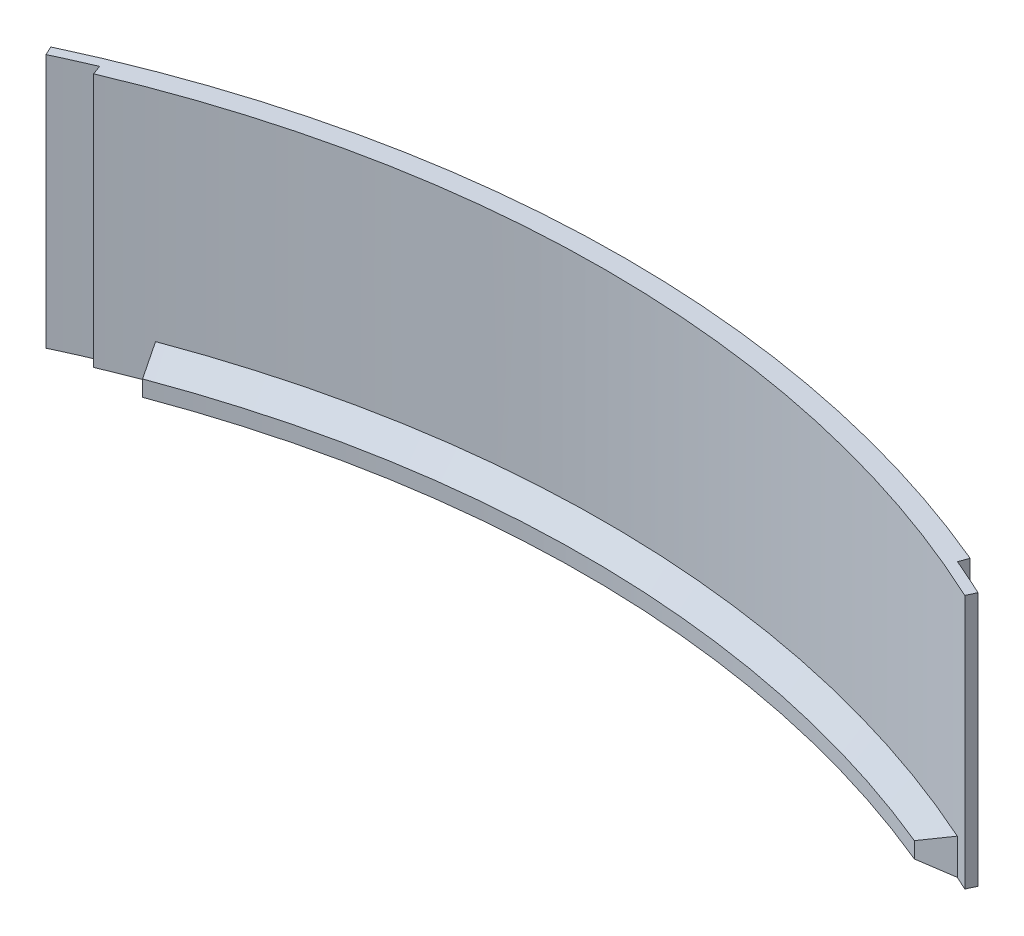
SolidWorks part; units mm, degrees
ref_plane "Front Plane" through (0, 0, 0) normal (0, 0, 1) x (1, 0, 0)
ref_plane "Top Plane" through (0, 0, 0) normal (0, 1, 0) x (1, 0, 0)
ref_plane "Right Plane" through (0, 0, 0) normal (1, 0, 0) x (0, 0, -1)
sketch "Sketch2" plane through (0, 0, 0) normal (0, 1, 0) x (1, 0, 0)
  line L0 (0, 0) -> (0, 184.9275) construction
  line L1 (-58.6379, 125.7494) -> (-59.1666, 126.8831)
  line L2 (58.11, 124.6173) -> (58.6379, 125.7494)
  line L3 (0, 0) -> (-58.11, 124.6173) construction
  line L4 (0, 0) -> (58.11, 124.6173) construction
  line L5 (-53.972, 127.8323) -> (-53.5408, 126.6477)
  line L6 (53.972, 127.8323) -> (53.5408, 126.6477) construction
  line L7 (53.972, 127.8323) -> (54.3969, 128.9999)
  line L8 (58.6379, 125.7494) -> (59.1666, 126.8831) construction
  line L9 (-58.11, 124.6173) -> (-58.6379, 125.7494) construction
  arc A0 (54.3969, 128.9999) -> (-59.1666, 126.8831) centre (0, 0) ccw
  arc A1 (58.11, 124.6173) -> (-53.5408, 126.6477) centre (0, 0) ccw
  arc A2 (-58.11, 124.6173) -> (58.11, 124.6173) centre (0, 0) ccw construction
  arc A3 (-59.1666, 126.8831) -> (59.1666, 126.8831) centre (0, 0) ccw construction
  arc A4 (-58.6379, 125.7494) -> (-53.972, 127.8323) centre (0, 0.6554) cw
  arc A5 (59.1666, 126.8831) -> (54.3969, 128.9999) centre (0, 0) ccw construction
  arc A6 (0, 138.8108) -> (53.972, 127.8323) centre (0, 0.6554) cw construction
  arc A7 (53.972, 127.8323) -> (58.6379, 125.7494) centre (0, 0.6554) cw
  arc A8 (-53.5408, 126.6477) -> (-58.11, 124.6173) centre (0, 0) ccw construction
  arc A9 (-53.972, 127.8323) -> (0, 138.8108) centre (0, 0.6554) cw construction
  dimension "D1" = 280
  dimension "D2" = 275
  dimension "D4" = 5
  dimension "D6" = 5.1097
  dimension "D3" = 50
  dimension "D5" = 5
extrude "Boss-Extrude1" add sketch "Sketch2" along normal mid plane 32
sketch "Sketch3" plane through (0, -16, 0) normal (0, -1, 0) x (1, 0, 0)
  line L0 (48.7183, -131.2499) -> (49.471, -133.6371)
  line L1 (53.972, -127.8323) -> (54.3969, -128.9999) construction
  line L2 (58.6379, -125.7494) -> (52.619, -127.0334)
  line L3 (-58.6379, -125.7494) -> (-53.5757, -129.3431)
  line L4 (54.5324, -131.6528) -> (53.5757, -129.3431) construction
  line L5 (-51.6623, -124.7237) -> (-52.619, -127.0334) construction
  line L6 (53.5757, -129.3431) -> (58.6379, -125.7494) construction
  line L7 (58.6379, -125.7494) -> (51.6623, -124.7237)
  line L8 (53.5757, -129.3431) -> (53.972, -127.8323)
  line L9 (-47.9655, -128.8625) -> (-47.2128, -126.4751)
  line L10 (-52.619, -127.0334) -> (-53.972, -127.8323)
  line L11 (-53.972, -127.8323) -> (-53.5408, -126.6477) construction
  line L12 (-52.619, -127.0334) -> (-58.6379, -125.7494) construction
  line L13 (-58.6379, -125.7494) -> (-54.5324, -131.6528)
  arc A0 (-54.5324, -131.6528) -> (49.471, -133.6371) centre (0, 0) ccw
  arc A1 (-53.5757, -129.3431) -> (48.7183, -131.2499) centre (0, 0) ccw construction
  arc A2 (-52.619, -127.0334) -> (52.619, -127.0334) centre (0, 0) ccw
  arc A3 (-53.5757, -129.3431) -> (53.5757, -129.3431) centre (0, 0) ccw
  arc A4 (-47.9655, -128.8625) -> (52.619, -127.0334) centre (0, 0) ccw construction
  arc A5 (-53.5757, -129.3431) -> (48.7183, -131.2499) centre (0, 0) ccw
  arc A6 (-47.9655, -128.8625) -> (52.619, -127.0334) centre (0, 0) ccw construction
  arc A7 (-47.2128, -126.4751) -> (51.6623, -124.7237) centre (0, 0) ccw
  arc A8 (49.471, -133.6371) -> (54.5324, -131.6528) centre (0, 0) ccw construction
  arc A9 (-54.5324, -131.6528) -> (54.5324, -131.6528) centre (0, 0) ccw construction
  arc A10 (48.7183, -131.2499) -> (53.4544, -129.3933) centre (0, 0) ccw construction
  arc A11 (-53.5757, -129.3431) -> (53.5757, -129.3431) centre (0, 0) ccw construction
  arc A12 (-58.6379, -125.7494) -> (-53.972, -127.8323) centre (0, -0.6554) ccw
  arc A13 (-58.6379, -125.7494) -> (-53.972, -127.8323) centre (0, -0.6554) ccw
  arc A14 (53.972, -127.8323) -> (58.6379, -125.7494) centre (0, -0.6554) ccw
  arc A15 (53.972, -127.8323) -> (58.6379, -125.7494) centre (0, -0.6554) ccw
  arc A16 (48.7183, -131.2499) -> (53.5757, -129.3431) centre (0, 0) ccw construction
  arc A17 (-53.5757, -129.3431) -> (53.5757, -129.3431) centre (0, 0) ccw construction
  arc A18 (-51.6623, -124.7237) -> (-47.2128, -126.4751) centre (0, 0) ccw construction
  arc A19 (-51.6623, -124.7237) -> (51.6623, -124.7237) centre (0, 0) ccw construction
  arc A20 (-52.619, -127.0334) -> (-47.9655, -128.8625) centre (0, 0) ccw construction
  arc A21 (-52.619, -127.0334) -> (52.619, -127.0334) centre (0, 0) ccw construction
  arc A22 (-52.619, -127.0334) -> (-47.9655, -128.8625) centre (0, 0) ccw construction
  arc A23 (-52.619, -127.0334) -> (52.619, -127.0334) centre (0, 0) ccw construction
  point P14 (-85.7288, -123.1804)
  dimension "D1" = 0
extrude "Boss-Extrude2" add sketch "Sketch3" against normal blind 2
chamfer "Chamfer2" distance 2.5 angle 45 6 edges at (-4.6013, -14, -139.9244) (4.5404, -14, -137.425) (-47.5892, -14, -127.6688) (54.0145, -14, -125.0696) (-55.884, -14, -129.7093) (49.0946, -14, -132.4435)
